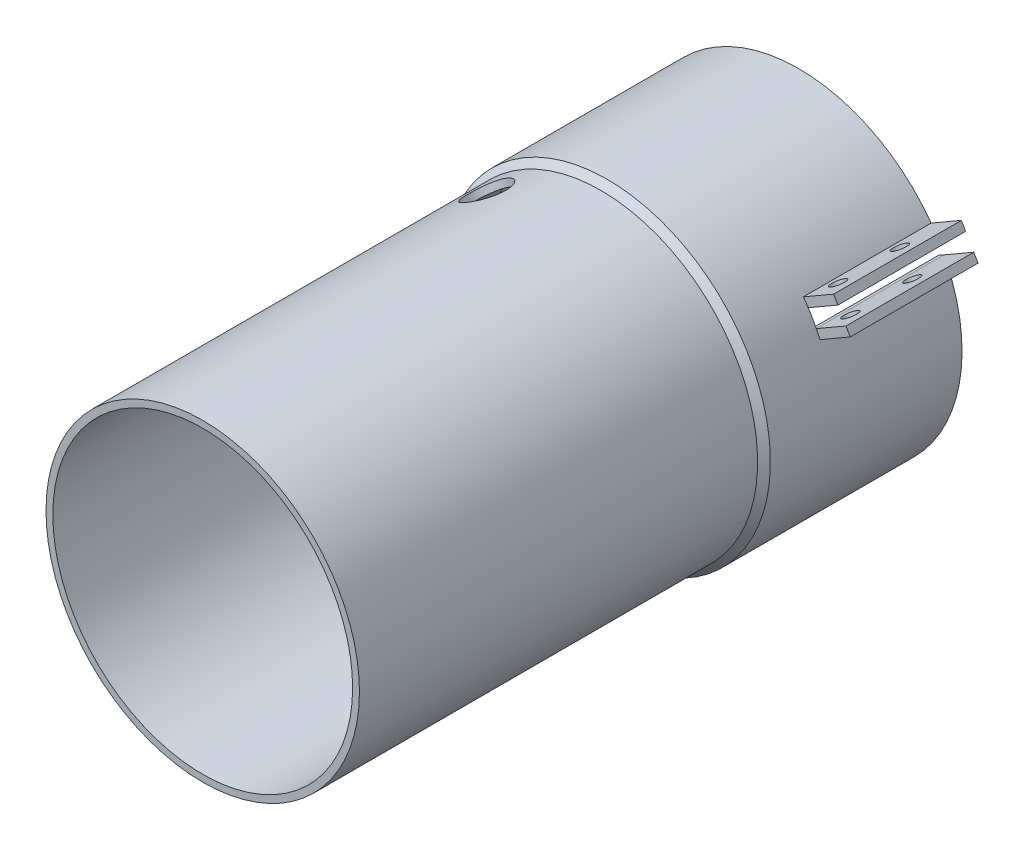
SolidWorks part; units mm, degrees
ref_plane "Front Plane" through (0, 0, 0) normal (0, 0, 1) x (1, 0, 0)
ref_plane "Top Plane" through (0, 0, 0) normal (0, 1, 0) x (1, 0, 0)
ref_plane "Right Plane" through (0, 0, 0) normal (1, 0, 0) x (0, 0, -1)
sketch "Sketch1" plane through (0, 0, 0) normal (0, 0, 1) x (1, 0, 0)
  circle A0 centre (0, 0) radius 35.2
  circle A1 centre (0, 0) radius 36.8
  dimension "D1" = 70.4
  dimension "D2" = 73.6
extrude "Boss-Extrude1" add sketch "Sketch1" along normal blind 100
sketch "Sketch2" plane through (0, 0, 0) normal (0, 0, -1) x (-1, 0, 0)
  circle A0 centre (0, 0) radius 36.8 construction
  circle A1 centre (0, 0) radius 36.8
  circle A2 centre (0, 0) radius 38.3
  dimension "D1" = 1.5
extrude "Boss-Extrude2" add sketch "Sketch2" along normal blind 10 and the other way blind 5
chamfer "Chamfer1" distance 1.5 1 edges at (-36.8, 0, 5)
sketch "Sketch6" plane through (0, 0, -10) normal (0, 0, -1) x (-1, 0, 0)
  line L0 (-40.0977, 23.1504) -> (40.0977, -23.1504) construction
  line L1 (-39.2477, 24.6226) -> (-40.9477, 21.6782) construction
  line L2 (40.9477, -21.6782) -> (39.2477, -24.6226) construction
  line L9 (-31.0464, 22.428) -> (-32.4312, 23.2275)
  line L10 (-32.4312, 23.2275) -> (-35.4623, 24.9775)
  line L11 (-35.4623, 24.9775) -> (-38.1477, 26.5279)
  line L12 (-36.4623, 23.2454) -> (-39.1477, 24.7958)
  line L13 (-33.4312, 21.4954) -> (-36.4623, 23.2454)
  line L14 (-30.9204, 20.0458) -> (-33.4312, 21.4954)
  line L15 (-36.4623, 23.2454) -> (-39.1477, 24.7958)
  line L16 (-33.4312, 21.4954) -> (-36.4623, 23.2454)
  line L17 (-32.1779, 20.7719) -> (-33.4312, 21.4954)
  line L18 (-39.1477, 24.7958) -> (-38.1477, 26.5279)
  line L19 (-34.9464, 15.673) -> (-36.3312, 16.4725)
  line L20 (-29.9204, 21.7779) -> (-32.4312, 23.2275) construction
  line L21 (-30.9204, 20.0458) -> (-33.4312, 21.4954) construction
  line L22 (-34.0779, 17.481) -> (-35.3312, 18.2046)
  line L23 (-35.3312, 18.2046) -> (-38.3623, 19.9546)
  line L24 (-38.3623, 19.9546) -> (-41.0477, 21.505)
  line L25 (-41.0477, 21.505) -> (-42.0477, 19.7729)
  line L26 (-39.3623, 18.2225) -> (-42.0477, 19.7729)
  line L27 (-36.3312, 16.4725) -> (-39.3623, 18.2225)
  line L28 (-32.1779, 20.7719) -> (-30.861, 20.0458)
  line L29 (-34.0779, 17.481) -> (-32.7433, 16.7963)
  line L30 (0, 0) -> (11.4159, 19.7729) construction
  line L31 (35.4623, -24.9775) -> (38.1477, -26.5279)
  line L32 (32.4312, -23.2275) -> (35.4623, -24.9775)
  line L33 (31.0464, -22.428) -> (32.4312, -23.2275)
  line L34 (32.1779, -20.7719) -> (30.9177, -19.9584)
  line L35 (32.1779, -20.7719) -> (33.4312, -21.4954)
  line L36 (33.4312, -21.4954) -> (36.4623, -23.2454)
  line L37 (36.4623, -23.2454) -> (39.1477, -24.7958)
  line L38 (39.1477, -24.7958) -> (38.1477, -26.5279)
  line L39 (41.0477, -21.505) -> (42.0477, -19.7729)
  line L40 (38.3623, -19.9546) -> (41.0477, -21.505)
  line L41 (35.3312, -18.2046) -> (38.3623, -19.9546)
  line L42 (34.0779, -17.481) -> (32.7907, -16.7035)
  line L43 (34.0779, -17.481) -> (35.3312, -18.2046)
  line L44 (34.9464, -15.673) -> (36.3312, -16.4725)
  line L45 (36.3312, -16.4725) -> (39.3623, -18.2225)
  line L46 (39.3623, -18.2225) -> (42.0477, -19.7729)
  arc A2 (-34.9464, 15.673) -> (31.0464, -22.428) centre (0, 0) ccw
  circle A3 centre (0, 0) radius 36.8 construction
  arc A4 (-32.7433, 16.7963) -> (30.9177, -19.9584) centre (0, 0) ccw
  arc A5 (32.7907, -16.7035) -> (-30.861, 20.0458) centre (0, 0) ccw
  arc A6 (34.9464, -15.673) -> (-31.0464, 22.428) centre (0, 0) ccw
  dimension "D1" = 0.2
  dimension "D2" = 2
extrude "Boss-Extrude3" add sketch "Sketch6" along normal blind 30
sketch "Sketch7" plane through (0, 0, 0) normal (0.5, -0.866, 0) x (0, 0, 1)
  line L0 (-26.75, 41.45) -> (-18.25, 41.45) construction
  arc A0 (-28.5, 39.7) -> (-28.5, 43.2) centre (-28.5, 41.45) ccw construction
  arc A1 (-16.5, 43.2) -> (-16.5, 39.7) centre (-16.5, 41.45) ccw construction
  circle A2 centre (-29.75, 41.45) radius 1.75
  circle A3 centre (-15.25, 41.45) radius 1.75
  dimension "D1" = 3.5
  dimension "D2" = 3.5
  dimension "D3" = 3
  dimension "D4" = 3
extrude "Cut-Extrude1" cut sketch "Sketch7" against normal through all and the other way through all
ref_plane "Plane3" through (0, 0, 0) normal (0.866, 0.5, 0) x (0, 0, 1)
mirror "Mirror1" about plane through (0, 0, 0) normal (0.866, 0.5, 0) of "Cut-Extrude1"
sketch "Sketch8" plane through (0, 0, -40) normal (0, 0, -1) x (-1, 0, 0)
  arc A14 (31.0857, -20.0668) -> (32.9689, -16.7943) centre (0, 0) ccw
  arc A15 (32.9689, -16.7943) -> (-31.0288, 20.1548) centre (0, 0) ccw
  arc A16 (-31.0288, 20.1548) -> (-32.9212, 16.8876) centre (0, 0) ccw
  arc A17 (-32.9212, 16.8876) -> (31.0857, -20.0668) centre (0, 0) ccw
  arc A18 (31.0857, -20.0668) -> (32.9689, -16.7943) centre (0, 0) ccw
  arc A19 (32.9689, -16.7943) -> (-31.0288, 20.1548) centre (0, 0) ccw
  arc A20 (-31.0288, 20.1548) -> (-32.9212, 16.8876) centre (0, 0) ccw
  arc A21 (-32.9212, 16.8876) -> (31.0857, -20.0668) centre (0, 0) ccw
  dimension "D1" = 0.2
extrude "Cut-Extrude2" cut sketch "Sketch8" against normal up to surface (40 mm away) up to face at (36.8, 0, 0)
ref_plane "Plane4" through (-18.4, 31.8697, 0) normal (-0.5, 0.866, 0) x (0.866, 0.5, 0)
sketch "Sketch9" plane through (-18.4, 31.8697, 0) normal (-0.5, 0.866, 0) x (0.866, 0.5, 0)
  line L0 (0, -5) -> (0, -41.8651) construction
  line L1 (38.3, -5) -> (-38.3, -5) construction
  circle A0 centre (0, -15) radius 5
  dimension "D1" = 10
  dimension "10mm" = 10
extrude "Cut-Extrude3" cut sketch "Sketch9" against normal up to next
